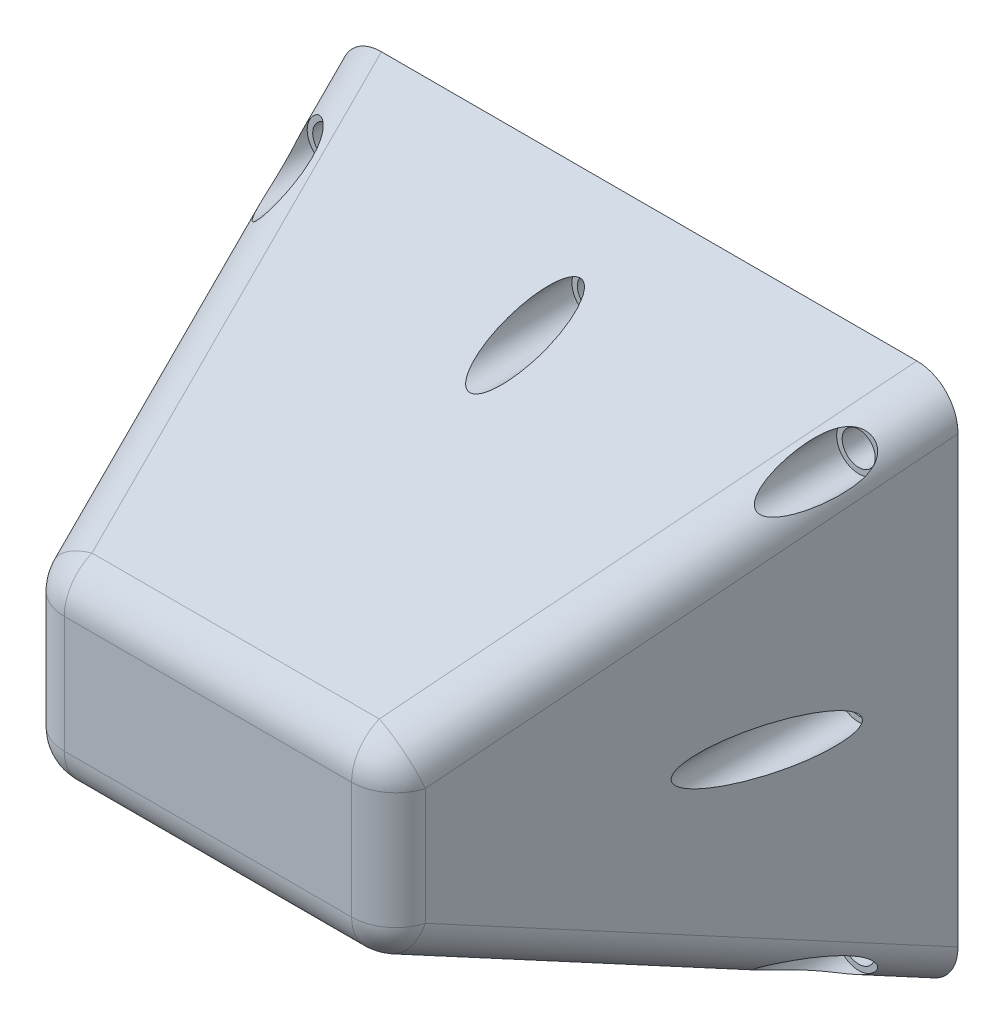
SolidWorks part; units mm, degrees
ref_plane "Front Plane" through (0, 0, 0) normal (0, 0, 1) x (1, 0, 0)
ref_plane "Top Plane" through (0, 0, 0) normal (0, 1, 0) x (1, 0, 0)
ref_plane "Right Plane" through (0, 0, 0) normal (1, 0, 0) x (0, 0, -1)
ref_plane "Plane1" through (0, -152.4, 0) normal (0, -1, 0) x (1, 0, 0)
sketch "Sketch1" plane through (0, -152.4, 0) normal (0, -1, 0) x (1, 0, 0)
  line L0 (177.8, 0) -> (0, 592.6667)
  line L1 (0, 592.6667) -> (-177.8, 0)
  line L2 (-177.8, 0) -> (177.8, 0)
extrude "Boss-Extrude1" add sketch "Sketch1" against normal blind 304.8
draft "Draft1" type of draft neutral plane draft angle 21.801 faces to draft 2 face at (0, 152.4, 197.5556) face at (0, -152.4, 197.5556) neutral plane through (-177.8, 152.4, 0) neutral plane normal (0, 0, -1) reverse direction yes parameters "D1"=21.801
chamfer "Chamfer1" distance 136.7832 angle 68.199 1 edges at (0, 0, 381) first distance on face at (0, -76.2, 190.5)
fillet "Fillet1" radius 25.4 4 edges at (139.7, -101.6, 127) (-139.7, -101.6, 127) (139.7, 101.6, 127) (-139.7, 101.6, 127) tangent propagation no
ref_plane "Plane2" through (0, 0, 103.1875) normal (0, 0, 1) x (1, 0, 0)
hole_wizard "Hole1" positions "Sketch3" profile "Sketch2" legacy
sketch "Sketch3" plane through (0, 0, 103.1875) normal (0, 0, 1) x (1, 0, 0)
  point P0 (0, 123.825)
  point P1 (0, -123.825)
sketch "Sketch2" plane through (0, 123.825, 103.1875) normal (1, 0, 0) x (0, -1, 0)
  line L0 (0, 0) -> (0, 103.1875)
  line L1 (0, 103.1875) -> (9.525, 103.1875)
  line L2 (9.525, 103.1875) -> (9.525, 71.4375)
  line L3 (9.525, 71.4375) -> (12.7, 71.4375)
  line L4 (12.7, 71.4375) -> (12.7, 0)
  line L5 (12.7, 0) -> (0, 0)
  line L6 (0, 110) -> (0, -10) construction
  dimension "Diameter" = 19.05
  dimension "Depth" = 103.1875
  dimension "C-Bore Diameter" = 25.4
  dimension "C-Bore Depth" = 71.4375
ref_plane "Plane3" through (0, 0, 127) normal (0, 0, 1) x (1, 0, 0)
hole_wizard "Hole2" positions "Sketch5" profile "Sketch4" legacy
sketch "Sketch5" plane through (0, 0, 127) normal (0, 0, 1) x (1, 0, 0)
  point P0 (152.4, 0)
  point P1 (-152.4, 0)
sketch "Sketch4" plane through (152.4, 0, 127) normal (1, 0, 0) x (0, -1, 0)
  line L0 (0, 0) -> (0, 127)
  line L1 (0, 127) -> (9.525, 127)
  line L2 (9.525, 127) -> (9.525, 95.25)
  line L3 (9.525, 95.25) -> (12.7, 95.25)
  line L4 (12.7, 95.25) -> (12.7, 0)
  line L5 (12.7, 0) -> (0, 0)
  line L6 (0, 110) -> (0, -10) construction
  dimension "Diameter" = 19.05
  dimension "Depth" = 127
  dimension "C-Bore Diameter" = 25.4
  dimension "C-Bore Depth" = 95.25
ref_plane "Plane4" through (0, 0, 82.7288) normal (0, 0, 1) x (1, 0, 0)
hole_wizard "Hole3" positions "Sketch7" profile "Sketch6" legacy
sketch "Sketch7" plane through (0, 0, 82.7288) normal (0, 0, 1) x (1, 0, 0)
  point P0 (152.4, 123.825)
  point P1 (-152.4, 123.825)
  point P2 (-152.4, -123.825)
  point P3 (152.4, -123.825)
sketch "Sketch6" plane through (152.4, 123.825, 82.7288) normal (1, 0, 0) x (0, -1, 0)
  line L0 (0, 0) -> (0, 82.7288)
  line L1 (0, 82.7288) -> (9.525, 82.7288)
  line L2 (9.525, 82.7288) -> (9.525, 50.9788)
  line L3 (9.525, 50.9788) -> (12.7, 50.9788)
  line L4 (12.7, 50.9788) -> (12.7, 0)
  line L5 (12.7, 0) -> (0, 0)
  line L6 (0, 110) -> (0, -10) construction
  dimension "Diameter" = 19.05
  dimension "Depth" = 82.7288
  dimension "C-Bore Diameter" = 25.4
  dimension "C-Bore Depth" = 50.9788
fillet "Fillet2" radius 25.4 8 edges at (-94.8081, 43.7934, 254) (-94.8081, -43.7934, 254) (94.8081, -43.7934, 254) (-101.6, 0, 254) (0, 50.8, 254) (0, -50.8, 254) (94.8081, 43.7934, 254) (101.6, 0, 254)
